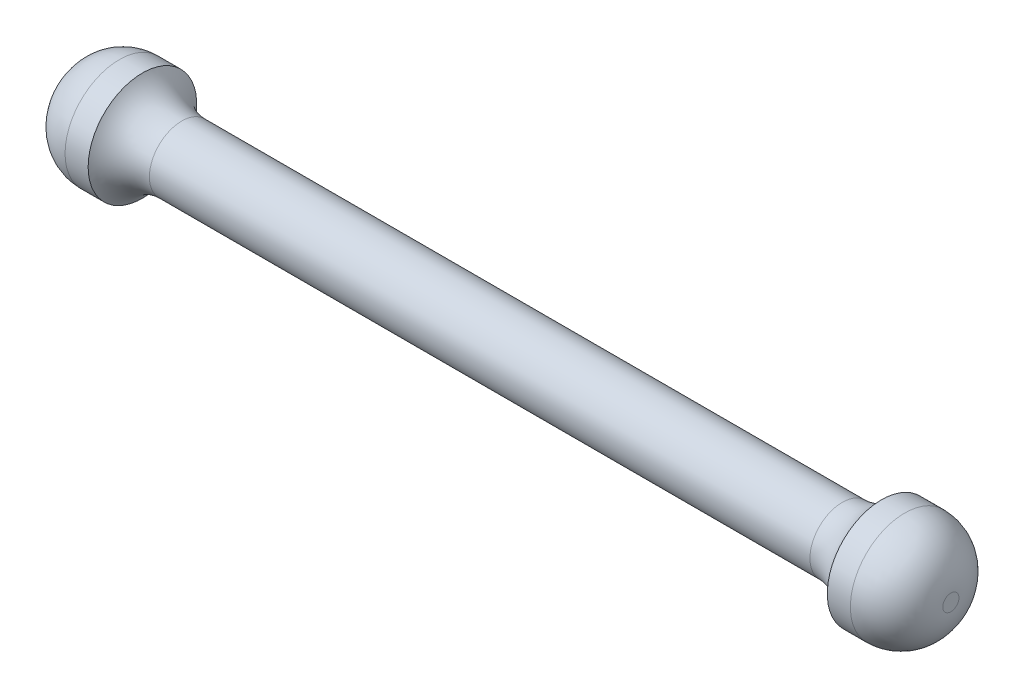
SolidWorks part; units mm, degrees
ref_plane "Front Plane" through (0, 0, 0) normal (0, 0, 1) x (1, 0, 0)
ref_plane "Top Plane" through (0, 0, 0) normal (0, 1, 0) x (1, 0, 0)
ref_plane "Right Plane" through (0, 0, 0) normal (1, 0, 0) x (0, 0, -1)
sketch "Sketch1" plane through (15, 0, 0) normal (1, 0, 0) x (0, 0, -1)
  circle A0 centre (32.2332, 33) radius 1.4
  dimension "D1" = 2.8
extrude "Boss-Extrude1" add sketch "Sketch1" against normal blind 32 from offset 1
sketch "Sketch2" plane through (16, 0, 0) normal (1, 0, 0) x (0, 0, -1)
  circle A0 centre (32.2332, 33) radius 2.35
  dimension "D1" = 4.7
extrude "Boss-Extrude2" add sketch "Sketch2" along normal blind 3
fillet "Fillet1" radius 2 2 edges at (16, 33, -33.6332) (19, 33, -34.5832)
sketch "Sketch3" plane through (-16, 0, 0) normal (-1, 0, 0) x (0, 0, 1)
  circle A0 centre (-32.2332, 33) radius 2.35
  dimension "D1" = 4.7
extrude "Boss-Extrude3" add sketch "Sketch3" along normal blind 3
fillet "Fillet2" radius 2 2 edges at (-16, 33, -33.6332) (-19, 33, -29.8832)
